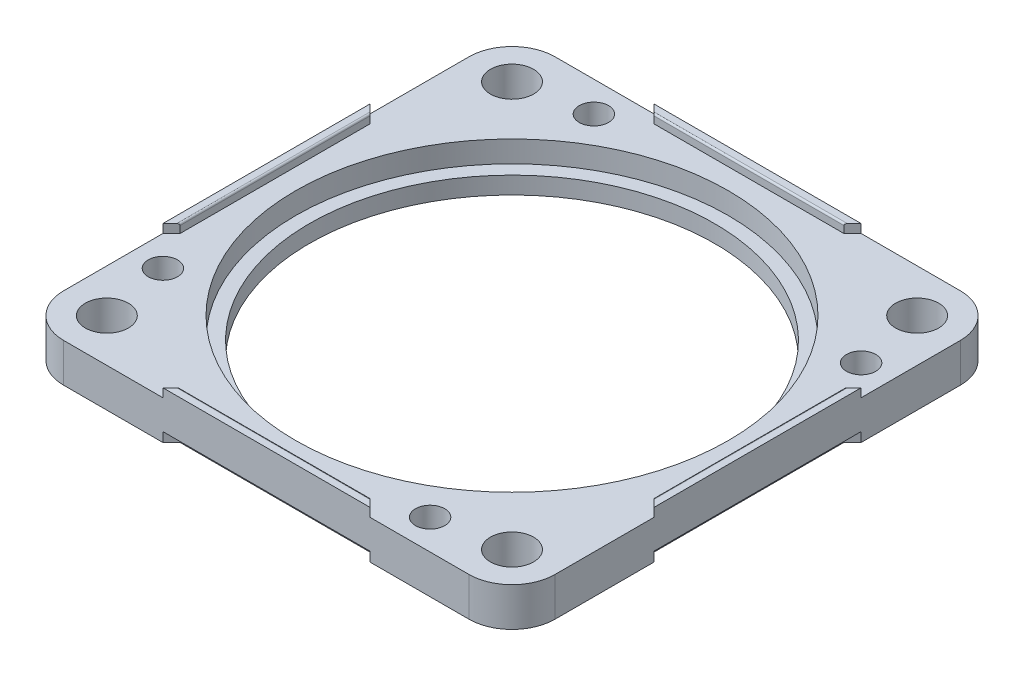
SolidWorks part; units mm, degrees
ref_plane "Front Plane" through (0, 0, 0) normal (0, 0, 1) x (1, 0, 0)
ref_plane "Top Plane" through (0, 0, 0) normal (0, 1, 0) x (1, 0, 0)
ref_plane "Right Plane" through (0, 0, 0) normal (1, 0, 0) x (0, 0, -1)
sketch "Sketch2" plane through (0, 0, 0) normal (0, 1, 0) x (1, 0, 0)
  line L1 (28.5, -28.5) -> (-28.5, -28.5)
  line L2 (28.5, -28.5) -> (28.5, 28.5)
  line L3 (28.5, 28.5) -> (-28.5, 28.5)
  line L4 (-28.5, -28.5) -> (-28.5, 28.5)
  line L5 (28.5, -28.5) -> (-28.5, 28.5) construction
  line L6 (28.5, 28.5) -> (-28.5, -28.5) construction
  circle A0 centre (0, 0) radius 23.5
  circle A1 centre (0, 0) radius 25.1
  point P0 (0, 0)
  dimension "D2" = 50.2
  dimension "D3" = 47
  dimension "D1" = 57
extrude "Boss-Extrude1" add sketch "Sketch2" along normal blind 4.5 contours L4 L1 L2 L3 A1 region at (0, 0, 27.6939)
extrude "Boss-Extrude2" add sketch "Sketch2<3>" along normal blind 2 contours A1 | A0
sketch "Sketch2<3>" plane through (0, 0, 0) normal (0, 1, 0) x (1, 0, 0) same geometry as "Sketch2"
fillet "Fillet1" radius 5 1 edges at (-28.5, 2.25, -28.5)
sketch "Sketch4" plane through (0, 4.5, 0) normal (0, 1, 0) x (1, 0, 0)
  line L4 (28.5, 28.5) -> (-23.5, 28.5)
  line L5 (-28.5, 23.5) -> (-28.5, -28.5)
  line L6 (-28.5, -28.5) -> (28.5, -28.5)
  line L7 (28.5, -28.5) -> (28.5, 28.5)
  line L8 (28.5, 28.5) -> (-23.5, 28.5)
  line L9 (-28.5, 23.5) -> (-28.5, -28.5)
  line L10 (-28.5, -28.5) -> (28.5, -28.5)
  line L11 (28.5, -28.5) -> (28.5, 28.5)
  circle A0 centre (-23.5, 23.5) radius 2.5
  arc A1 (-23.5, 28.5) -> (-28.5, 23.5) centre (-23.5, 23.5) ccw
  arc A2 (-23.5, 28.5) -> (-28.5, 23.5) centre (-23.5, 23.5) ccw
  circle A3 centre (-15.5, 25) radius 1.7
  dimension "D2" = 5
  dimension "D3" = 3.4
  dimension "D4" = 8
  dimension "D5" = 3.5
  dimension "D1" = 0
extrude "Cut-Extrude1" cut sketch "Sketch4" against normal through all contours A3 | A0
sketch "Sketch5" plane through (0, 4.5, 0) normal (0, 1, 0) x (1, 0, 0)
  line L0 (0, 0) -> (0, 38.8962) construction
  line L1 (11, 27.5) -> (-11, 27.5)
  line L2 (-11, 27.5) -> (-12, 28.5)
  line L3 (28.5, 28.5) -> (-23.5, 28.5) construction
  line L4 (11, 27.5) -> (12, 28.5)
  line L5 (12, 28.5) -> (-12, 28.5)
  point P9 (0, 27.5)
  dimension "D1" = 11
  dimension "D2" = 135
  dimension "D3" = 1
extrude "Boss-Extrude3" add sketch "Sketch5" along normal blind 1
fillet "Fillet2" radius 0.2 1 edges at (0, 5.5, -27.5)
sketch "Sketch6" plane through (0, 0, 0) normal (0, -1, 0) x (1, 0, 0)
  line L4 (11, -27.5) -> (-11, -27.5)
  line L5 (-11, -27.5) -> (-12, -28.5)
  line L6 (-12, -28.5) -> (12, -28.5)
  line L7 (12, -28.5) -> (11, -27.5)
  line L8 (11, -27.5) -> (-11, -27.5)
  line L9 (-11, -27.5) -> (-12, -28.5)
  line L10 (-12, -28.5) -> (12, -28.5)
  line L11 (12, -28.5) -> (11, -27.5)
  dimension "D1" = 0
extrude "Cut-Extrude2" cut sketch "Sketch6" against normal blind 1.1
pattern_circular "CirPattern7" count 4 over 360 about axis through (0, 2, 0) along (0, 1, 0) of "Cut-Extrude1", "Boss-Extrude3", "Fillet2", "Cut-Extrude2"
fillet "Fillet3" radius 5 3 edges at (28.5, 2.25, -28.5) (28.5, 2.25, 28.5) (-28.5, 2.25, 28.5)
